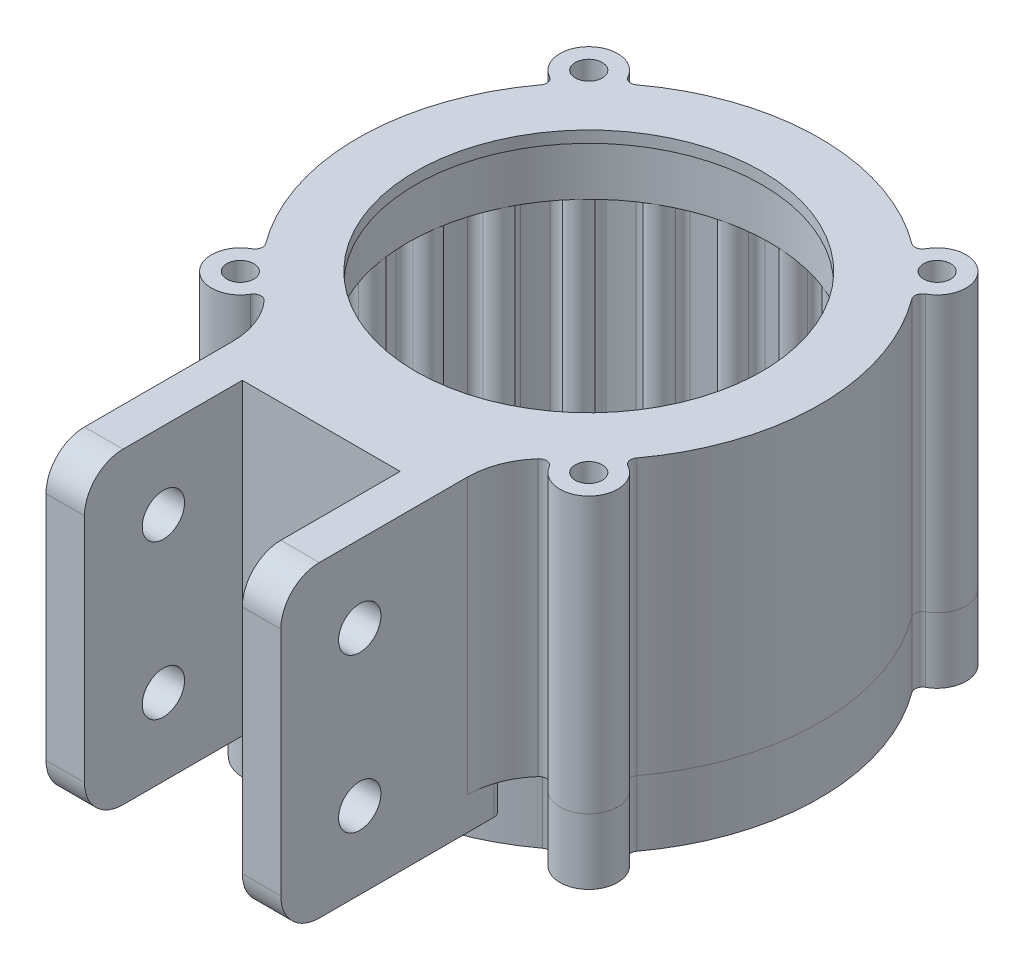
SolidWorks part; units mm, degrees
ref_plane "Front Plane" through (0, 0, 0) normal (0, 0, 1) x (1, 0, 0)
ref_plane "Top Plane" through (0, 0, 0) normal (0, 1, 0) x (1, 0, 0)
ref_plane "Right Plane" through (0, 0, 0) normal (1, 0, 0) x (0, 0, -1)
ref_axis "Housing Axis" through (0, 20.875, 0) along (0, -1, 0)
sketch "Sketch1" plane through (0, 0, 0) normal (0, 1, 0) x (1, 0, 0)
  line L0 (0, 0) -> (26.1689, 3.9443) construction
  line L1 (0, 0) -> (26.1689, -3.9443) construction
  line L2 (0, 0) -> (25, 0) construction
  line L3 (26.1689, 3.9443) -> (29.6649, 4.4713)
  line L4 (26.1689, -3.9443) -> (29.6649, -4.4713)
  circle A0 centre (0, 0) radius 25 construction
  arc A1 (25.2063, 1.4858) -> (25.2062, -1.4858) centre (25, 0) ccw
  arc A2 (26.1689, 3.9443) -> (26.339, 2.5735) centre (0, 0) cw
  arc A3 (26.339, -2.5735) -> (26.1689, -3.9443) centre (0, 0) cw
  arc A4 (25.2063, 1.4858) -> (26.339, 2.5735) centre (25.3438, 2.4763) ccw
  arc A5 (25.2062, -1.4858) -> (26.339, -2.5735) centre (25.3438, -2.4763) cw
  arc A6 (25.2063, 1.4858) -> (25.2063, -1.4858) centre (0, 0) cw construction
  arc A7 (29.6649, 4.4713) -> (29.6649, -4.4713) centre (0, 0) cw
  point P14 (26.4623, -0.3341)
  dimension "D1" = 50
  dimension "D2" = 3
  dimension "D5" = 1
  dimension "D6" = 30
  dimension "D3" = 17.143
  dimension "D4" = 0.25
extrude "Boss-Extrude1" add sketch "Sketch1" along normal mid plane 27.25
sketch "Sketch2" plane through (0, 13.625, 0) normal (0, 1, 0) x (1, 0, 0)
  circle A0 centre (0, 0) radius 30
  circle A1 centre (0, 0) radius 22.5
  circle A2 centre (0, 0) radius 30 construction
  dimension "D1" = 45
extrude "Boss-Extrude2" add sketch "Sketch2" along normal blind 8.5
pattern_circular "CirPattern1" count 21 over 360 about axis through (0, 20.875, 0) along (0, -1, 0) of "Boss-Extrude1"
sketch "Sketch3" plane through (0, 22.125, 0) normal (0, -1, 0) x (-1, 0, 0)
  circle A0 centre (0, 0) radius 23.5
  dimension "D1" = 47
extrude "Cut-Extrude1" cut sketch "Sketch3" along normal through all from offset 1.5
sketch "Sketch4" plane through (0, 22.125, 0) normal (0, 1, 0) x (1, 0, 0)
  line L0 (-10.25, -55.25) -> (-10.25, -34.75)
  line L1 (-10.25, -34.75) -> (10.25, -34.75)
  line L2 (10.25, -34.75) -> (10.25, -55.25)
  line L3 (10.25, -55.25) -> (-10.25, -34.75) construction
  line L4 (0, -45) -> (0, 0) construction
  line L5 (10.25, -55.25) -> (15.25, -55.25)
  line L6 (15.25, -55.25) -> (15.25, -25.8348)
  line L7 (-10.25, -55.25) -> (-15.25, -55.25)
  line L8 (-15.25, -55.25) -> (-15.25, -25.8348)
  circle A0 centre (0, 0) radius 30 construction
  arc A1 (15.25, -25.8348) -> (-15.25, -25.8348) centre (0, 0) cw
  point P14 (0, 0)
  dimension "D3" = 5
  dimension "D1" = 20.5
  dimension "D2" = 45
extrude "Boss-Extrude3" add sketch "Sketch4" against normal blind 40
fillet "Fillet1" radius 10 2 edges at (15.25, 4.25, 25.8348) (-15.25, 4.25, 25.8348)
fillet "Fillet2" radius 1 2 edges at (-15.25, -15.75, 25.8348) (15.25, -15.75, 25.8348)
sketch "Sketch5" plane through (15.25, 0, 0) normal (1, 0, 0) x (0, 0, -1)
  line L0 (-45, 22.125) -> (-45, 12.125) construction
  line L1 (-55.25, 22.125) -> (-31.0232, 22.125) construction
  line L2 (-45, 12.125) -> (-45, -7.875) construction
  line L3 (-45, -7.875) -> (-45, -17.875) construction
  line L4 (-55.25, -17.875) -> (-27.5307, -17.875) construction
  line L5 (-55.25, 22.125) -> (-34.75, 22.125) construction
  circle A0 centre (-45, 12.125) radius 2.75
  circle A1 centre (-45, -7.875) radius 2.75
  point P10 (0, 0)
  dimension "D2" = 5.5
  dimension "D1" = 20
extrude "Cut-Extrude2" cut sketch "Sketch5" against normal through all both
fillet "Fillet3" radius 5 4 edges at (12.75, -17.875, 55.25) (-12.75, -17.875, 55.25) (12.75, 22.125, 55.25) (-12.75, 22.125, 55.25)
sketch "Sketch6" plane through (0, -13.625, 0) normal (0, -1, 0) x (1, 0, 0)
  line L0 (0, 0) -> (22.6274, 22.6274) construction
  line L1 (0, 0) -> (22.6274, -22.6274) construction
  line L2 (0, 0) -> (-22.6274, -22.6274) construction
  line L3 (0, 0) -> (-22.6274, 22.6274) construction
  line L4 (-22.6274, 22.6274) -> (22.6274, 22.6274) construction
  line L5 (22.6274, 22.6274) -> (22.6274, -22.6274) construction
  line L6 (-15.25, 31.0232) -> (15.25, 31.0232)
  circle A0 centre (22.6274, 22.6274) radius 1.75
  circle A1 centre (22.6274, -22.6274) radius 1.75
  circle A2 centre (-22.6274, -22.6274) radius 1.75
  circle A3 centre (-22.6274, 22.6274) radius 1.75
  arc A4 (24.4256, 19.3366) -> (19.3943, 24.5273) centre (22.6274, 22.6274) ccw
  arc A5 (19.3366, -24.4256) -> (24.4256, -19.3366) centre (22.6274, -22.6274) ccw
  arc A6 (-24.4256, -19.3366) -> (-19.3366, -24.4256) centre (-22.6274, -22.6274) ccw
  arc A7 (-19.3943, 24.5273) -> (-24.4256, 19.3366) centre (-22.6274, 22.6274) ccw
  arc A8 (-18.9375, 23.2674) -> (-15.25, 31.0232) centre (-25.25, 31.0232) ccw construction
  arc A9 (24.1017, 17.8636) -> (24.4256, 19.3366) centre (24.9051, 18.4591) cw
  arc A10 (15.25, 31.0232) -> (18.9375, 23.2674) centre (25.25, 31.0232) ccw construction
  arc A11 (-18.9375, 23.2674) -> (-18.9331, 23.271) centre (-25.25, 31.0232) ccw
  arc A12 (-17.8636, -24.1017) -> (17.8636, -24.1017) centre (0, 0) ccw
  arc A13 (15.25, 31.0232) -> (17.7857, 24.3685) centre (25.25, 31.0232) ccw
  arc A14 (-24.1017, 17.8636) -> (-24.1017, -17.8636) centre (0, 0) ccw
  arc A15 (24.1017, -17.8636) -> (24.1017, 17.8636) centre (0, 0) ccw
  arc A16 (-18.9375, 23.2674) -> (18.9375, 23.2674) centre (0, 0) ccw construction
  arc A17 (24.4256, -19.3366) -> (24.1017, -17.8636) centre (24.9051, -18.4591) cw
  arc A18 (17.8636, -24.1017) -> (19.3366, -24.4256) centre (18.4591, -24.9051) cw
  arc A19 (-19.3366, -24.4256) -> (-17.8636, -24.1017) centre (-18.4591, -24.9051) cw
  arc A20 (-24.4256, -19.3366) -> (-24.1017, -17.8636) centre (-24.9051, -18.4591) ccw
  arc A21 (-24.4256, 19.3366) -> (-24.1017, 17.8636) centre (-24.9051, 18.4591) cw
  arc A22 (-19.3943, 24.5273) -> (-17.7857, 24.3685) centre (-18.5322, 25.034) ccw
  arc A23 (17.7857, 24.3685) -> (19.3943, 24.5273) centre (18.5322, 25.034) ccw
  arc A24 (-17.7857, 24.3685) -> (-15.25, 31.0232) centre (-25.25, 31.0232) ccw
  circle A25 centre (0, 0) radius 26.4644
  arc A26 (20.3126, 16.9636) -> (18.4341, 18.9881) centre (0, 0) ccw construction
  point P13 (0, 0)
  point P36 (-18.9331, -23.271)
  dimension "D1" = 4
  dimension "D3" = 3.5
  dimension "D4" = 7.5
  dimension "D5" = 1
  dimension "D2" = 32
extrude "Boss-Extrude4" add sketch "Sketch6" against normal up to surface (35.75 mm away) contours A24 A22 A7 A21 A14 A20 A6 A19 A12 A18 A5 A17 A15 A9 A4 A23 A13 L6 A25 A3 A2 A1 A0 region at (0, -13.625, 30.1674) up to face at (0, 22.125, 32.4982)
sketch "Sketch7" plane through (0, -13.625, 0) normal (0, -1, 0) x (1, 0, 0)
  arc A0 (-19.163, 24.0628) -> (-24.4256, 19.3366) centre (-22.6274, 22.6274) ccw
  arc A1 (-24.4256, -19.3366) -> (-19.3366, -24.4256) centre (-22.6274, -22.6274) ccw
  arc A2 (24.4256, 19.3366) -> (19.163, 24.0628) centre (22.6274, 22.6274) ccw
  arc A3 (19.3366, -24.4256) -> (24.4256, -19.3366) centre (22.6274, -22.6274) ccw
  circle A4 centre (-22.6274, 22.6274) radius 1.75 construction
  circle A5 centre (-22.6274, -22.6274) radius 1.75 construction
  circle A6 centre (22.6274, -22.6274) radius 1.75 construction
  circle A7 centre (22.6274, 22.6274) radius 1.75 construction
  circle A8 centre (-22.6274, 22.6274) radius 1.75
  circle A9 centre (-22.6274, -22.6274) radius 1.75
  circle A10 centre (22.6274, -22.6274) radius 1.75
  circle A11 centre (22.6274, 22.6274) radius 1.75
  arc A12 (-19.3943, 24.5273) -> (-24.4256, 19.3366) centre (-22.6274, 22.6274) ccw construction
  arc A13 (-24.4256, -19.3366) -> (-24.1017, -17.8636) centre (-24.9051, -18.4591) ccw construction
  arc A14 (-24.1017, 17.8636) -> (-24.1017, -17.8636) centre (0, 0) ccw construction
  arc A15 (-24.1017, 17.8636) -> (-24.4256, 19.3366) centre (-24.9051, 18.4591) ccw construction
  arc A16 (-24.4256, -19.3366) -> (-24.1017, -17.8636) centre (-24.9051, -18.4591) ccw
  arc A17 (-24.1017, 17.8636) -> (-24.1017, -17.8636) centre (0, 0) ccw
  arc A18 (-24.1017, 17.8636) -> (-24.4256, 19.3366) centre (-24.9051, 18.4591) ccw
  arc A22 (24.1017, -17.8636) -> (24.4256, -19.3366) centre (24.9051, -18.4591) ccw
  arc A23 (24.1017, -17.8636) -> (24.1017, 17.8636) centre (0, 0) ccw
  arc A24 (24.4256, 19.3366) -> (24.1017, 17.8636) centre (24.9051, 18.4591) ccw
  arc A25 (-17.8636, -24.1017) -> (-19.3366, -24.4256) centre (-18.4591, -24.9051) ccw
  arc A26 (-17.8636, -24.1017) -> (17.8636, -24.1017) centre (0, 0) ccw
  arc A27 (19.3366, -24.4256) -> (17.8636, -24.1017) centre (18.4591, -24.9051) ccw
  circle A28 centre (0, 0) radius 23.5
  circle A29 centre (0, 0) radius 23.5 construction
  arc A30 (17.8636, 24.1017) -> (-17.8636, 24.1017) centre (0, 0) ccw [skipped]
  arc A31 (17.8636, 24.1017) -> (19.3366, 24.4256) centre (18.4591, 24.9051) ccw [skipped]
  arc A32 (-19.3366, 24.4256) -> (-17.8636, 24.1017) centre (-18.4591, 24.9051) ccw [skipped]
  arc A33 (17.6411, 23.644) -> (-17.6411, 23.644) centre (0, 0) ccw
  arc A34 (13.7903, 26.6426) -> (-13.7903, 26.6426) centre (0, 0) ccw construction
  arc A35 (17.6411, 23.644) -> (19.163, 24.0628) centre (18.2391, 24.4455) ccw
  arc A36 (-17.6411, 23.644) -> (-19.163, 24.0628) centre (-18.2391, 24.4455) cw
  point P35 (0, 0)
  point P37 (18.8965, 22.2492)
  point P38 (18.4591, 22.2492)
  point P55 (0, 0)
  dimension "D1" = 4
  dimension "D2" = 0.5
extrude "Boss-Extrude5" add sketch "Sketch7" along normal blind 8.5 separate body
sketch "Sketch8" plane through (0, -22.125, 0) normal (0, -1, 0) x (1, 0, 0)
  circle A0 centre (0, 0) radius 22.5
  circle A1 centre (0, 0) radius 22.5 construction
  circle A2 centre (0, 0) radius 23.5 construction
  circle A3 centre (0, 0) radius 23.5
extrude "Boss-Extrude6" add sketch "Sketch8" against normal blind 1.5
sketch "Sketch9" plane through (0, -22.125, 0) normal (0, -1, 0) x (1, 0, 0)
  line L0 (0, 0) -> (-19.8823, 19.8823) construction
  line L1 (-27.291, 12.4736) -> (-12.4736, 27.291) construction
  line L2 (0, 0) -> (0, 29.5) construction
  circle A0 centre (-27.291, 12.4736) radius 2.35
  circle A1 centre (-12.4736, 27.291) radius 2.35
  arc A2 (17.6411, 23.644) -> (-17.6411, 23.644) centre (0, 0) ccw construction
  circle A3 centre (-12.4736, 27.291) radius 5
  circle A4 centre (-27.291, 12.4736) radius 5
  dimension "D1" = 20.955
  dimension "D2" = 4.7
  dimension "D5" = 10
  dimension "D3" = 28.1178
  dimension "D4" = 45
extrude "Boss-Extrude7" add sketch "Sketch9" along normal blind 2.856 and the other way blind 2
sketch "Sketch10" plane through (0, -24.981, 0) normal (0, -1, 0) x (1, 0, 0)
  circle A0 centre (-27.291, 12.4736) radius 2.35 construction
  circle A1 centre (-12.4736, 27.291) radius 2.35 construction
  circle A2 centre (-27.291, 12.4736) radius 2.35
  circle A3 centre (-12.4736, 27.291) radius 2.35
extrude "Cut-Extrude3" cut sketch "Sketch10" against normal blind 4
sketch "Sketch11" plane through (0, -20.125, 0) normal (0, 1, 0) x (1, 0, 0)
  circle A0 centre (-27.291, -12.4736) radius 5 construction
  circle A1 centre (-12.4736, -27.291) radius 5 construction
  circle A2 centre (-27.291, -12.4736) radius 5
  circle A3 centre (-12.4736, -27.291) radius 5
extrude "Boss-Extrude8" add sketch "Sketch11" against normal up to surface (0.856 mm away) up to face at (-26.2194, -20.981, 11.9838)
chamfer "Chamfer1" distance 6 angle 45 2 edges at (-27.2851, -20.125, 12.4709) (-12.263, -20.125, 26.8304)
sketch "Sketch12" plane through (0, -17.875, 0) normal (0, -1, 0) x (1, 0, 0)
  circle A0 centre (-12.4736, 27.291) radius 5.5
  circle A1 centre (-12.4736, 27.291) radius 5 construction
  dimension "D1" = 0.5
extrude "Cut-Extrude4" cut sketch "Sketch12" against normal up to vertex (3.75 mm away) up to point (-16.5617, -14.125, 24.4123)
equation "\"RotorRadius\"= 25mm"
equation "\"Eccentricity\"= 1.00mm"
equation "\"RollerRadius\"= 1.5mm"
equation "\"GearRatio\"= 20"
equation "\"RollerCount\"=\"GearRatio\" + 1"
equation "\"RotorThickness\"= 6mm"
equation "\"OutputRollerRadius\"= 1.5mm"
equation "\"OutputRollerCount\"= 6"
equation "\"OutputRollerHoleCircleRadius\"=\"RotorRadius\"- 4 * \"OutputRollerRadius\""
equation "\"RotorGap\"= 0.5mm"
equation "\"D1@Sketch1\"=\"RotorRadius\"*2"
equation "\"D2@Sketch1\"=2*\"RollerRadius\""
equation "\"rotorCount\"= 2"
equation "\"D1@Boss-Extrude1\"=(\"rotorCount\" + 2) * \"RotorThickness\" + 0.5mm * (\"rotorCount\" + 4.5)"
equation "\"D1@CirPattern1\"=\"GearRatio\" + 1"
equation "\"D3@Sketch1\"=360deg/(\"GearRatio\" + 1)"
